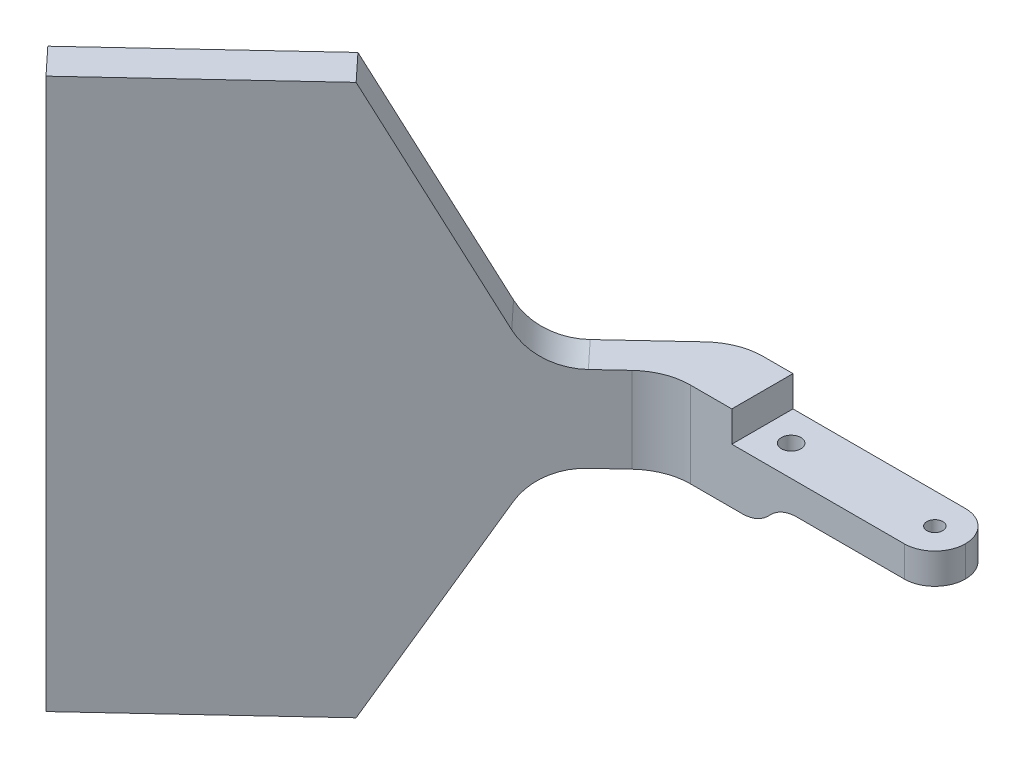
SolidWorks part; units mm, degrees
ref_plane "Front" through (0, 0, 0) normal (0, 0, 1) x (1, 0, 0)
ref_plane "Top" through (0, 0, 0) normal (0, 1, 0) x (1, 0, 0)
ref_plane "Right" through (0, 0, 0) normal (1, 0, 0) x (0, 0, -1)
sketch "Sketch1" plane through (0, 0, 0) normal (0, 1, 0) x (1, 0, 0)
  line L0 (0, 10) -> (0, 0)
  line L1 (0, 0) -> (42, 0)
  line L3 (0, 10) -> (42, 10)
  line L4 (42, 0) -> (42, 10)
  line L9 (0, 10) -> (-58.5083, -44.5599)
  line L10 (-58.5083, -44.5599) -> (-54.4163, -48.948)
  line L11 (0, 10) -> (4.092, 5.6119)
  line L12 (-54.4163, -48.948) -> (4.092, 5.6119)
  line L13 (0, 0) -> (-1.926, 0)
  line L14 (-1.926, 0) -> (0, 1.796)
  line L15 (0, 1.796) -> (0, 0)
  dimension "D1" = 10
  dimension "D2" = 42
  dimension "D3" = 223
  dimension "D4" = 80
  dimension "D5" = 6
  dimension "D6" = 270
extrude "Boss-Extrude1" add sketch "Sketch1" along normal blind 5 contours L10 L12 L1 L0 L9 | L1 L12 L11 L0 | L12 L1 L4 L3 L11 | L13 L0 L12 region at (1.364, 0, -5.8026) region at (-28.2435, 0, 20.3899) region at (21.8174, 0, -4.9666) region at (-0.642, 0, -0.5987)
fillet "Fillet1" radius 5 2 edges at (42, 2.5, 0) (42, 2.5, -10)
sketch "Sketch2" plane through (0, 5, 0) normal (0, 1, 0) x (1, 0, 0)
  circle A0 centre (37, 5) radius 1.3
extrude "Cut-Extrude1" cut sketch "Sketch2" against normal blind 10
sketch "Sketch3" plane through (0, 5, 0) normal (0, 1, 0) x (1, 0, 0)
  line L0 (-58.5083, -44.5599) -> (-54.4163, -48.948)
  line L1 (-54.4163, -48.948) -> (-28.1712, -24.474)
  line L2 (-54.4163, -48.948) -> (-1.926, 0) construction
  line L3 (-28.1712, -24.474) -> (-32.2631, -20.0859)
  line L4 (0, 10) -> (-58.5083, -44.5599) construction
  line L5 (-32.2631, -20.0859) -> (-58.5083, -44.5599)
extrude "Boss-Extrude2" add sketch "Sketch3" along normal blind 45
sketch "Sketch4" plane through (0, 0, 0) normal (0, -1, 0) x (1, 0, 0)
  line L0 (-58.5083, 44.5599) -> (-54.4163, 48.948)
  line L1 (-54.4163, 48.948) -> (-28.1712, 24.474)
  line L2 (-54.4163, 48.948) -> (-1.926, 0) construction
  line L3 (-28.1712, 24.474) -> (-32.2631, 20.0859)
  line L4 (0, -10) -> (-58.5083, 44.5599) construction
  line L5 (-32.2631, 20.0859) -> (-58.5083, 44.5599)
extrude "Boss-Extrude3" add sketch "Sketch4" along normal blind 40
sketch "Sketch5" plane through (-4.9878, 0, -5.3488) normal (-0.682, 0, -0.7314) x (-0.7314, 0, 0.682)
  line L0 (37.2943, -40) -> (37.2943, 0)
  line L1 (37.2943, 0) -> (13.889, 0)
  line L2 (-6.82, 0) -> (37.2943, 0) construction
  line L3 (13.889, 0) -> (37.2943, -40)
  line L4 (13.889, 5) -> (37.2943, 50)
  line L5 (-6.82, 5) -> (37.2943, 5) construction
  line L6 (37.2943, 50) -> (37.2943, 5)
  line L7 (37.2943, 5) -> (13.889, 5)
extrude "Boss-Extrude4" add sketch "Sketch5" against normal blind 6
sketch "Sketch6" plane through (0, 0, 0) normal (0, -1, 0) x (1, 0, 0)
  circle A0 centre (37, -5) radius 4.9
  circle A1 centre (37, -5) radius 1.3
extrude "Boss-Extrude5" [suppressed] add sketch "Sketch6" against normal blind 5.9
sketch "Sketch8" plane through (0, 0, 0) normal (0, -1, 0) x (1, 0, 0)
  line L0 (0, -10) -> (-23.7044, 12.1047)
  line L1 (-32.2631, 20.0859) -> (-15.1456, 4.1235) construction
  line L6 (-23.7044, 12.1047) -> (-19.6124, 16.4928)
  line L7 (-28.1712, 24.474) -> (-11.0536, 8.5116) construction
  line L8 (-19.6124, 16.4928) -> (8.7977, -10)
  line L9 (0, -10) -> (37, -10) construction
  line L10 (8.7977, -10) -> (0, -10)
extrude "Boss-Extrude6" add sketch "Sketch8" along normal blind 4
sketch "Sketch9" plane through (0, 5, 0) normal (0, 1, 0) x (1, 0, 0)
  line L3 (-16.8573, -5.7197) -> (-32.2631, -20.0859) construction
  line L4 (-24.5602, -12.9028) -> (0, 10)
  line L6 (-24.5602, -12.9028) -> (-16.7996, -13.8699)
  line L7 (-28.1712, -24.474) -> (-11.0536, -8.5116) construction
  line L9 (-16.7996, -13.8699) -> (8.7977, 10)
  line L10 (0, 10) -> (37, 10) construction
  line L11 (8.7977, 10) -> (0, 10)
  line L12 (37, 0) -> (-1.926, 0) construction
  line L13 (8.7977, 0) -> (-1.926, 0)
  line L14 (-1.926, 0) -> (8.7977, 10)
  line L15 (8.7977, 10) -> (17.9505, 10)
  line L16 (17.9505, 10) -> (17.9505, 0)
  line L17 (17.9505, 0) -> (8.7977, 0)
  line M3 (-1.926, 0) -> (37, 0)
  line M6 (37, 10) -> (0, 10)
sketch "Sketch10" plane through (0, 5, 0) normal (0, 1, 0) x (1, 0, 0)
  line L0 (8.7977, 10) -> (8.7977, 0)
  line L1 (8.7977, 0) -> (-1.926, 0)
  line L2 (-1.926, 0) -> (-16.7996, -13.8699)
  line L3 (-16.7996, -13.8699) -> (-20.8916, -9.4817)
  line L4 (-20.8916, -9.4817) -> (0, 10)
  line L5 (0, 10) -> (8.7977, 10)
extrude "Boss-Extrude7" add sketch "Sketch10" along normal blind 5
extrude "Boss-Extrude8" add sketch "Sketch9" against normal blind 9 contours L16 L9 M6 M3 region at (10.3631, 5, -4.3843)
chamfer "Chamfer1" distance 5 angle 45 1 edges at (17.9505, -4, -5)
fillet "Fillet2" radius 6 2 edges at (16.9505, 0, -5) (12.9505, -4, -5)
sketch "Sketch11" plane through (0, 5, 0) normal (0, 1, 0) x (1, 0, 0)
  circle A0 centre (13.5, 5) radius 1.6
extrude "Cut-Extrude2" cut sketch "Sketch11" against normal blind 10
fillet "Fillet3" radius 10 4 edges at (0, 3, -10) (-14.8113, -4, 7.9138) (-15.0015, 10, 8.0911) (-1.926, 3, 0)
